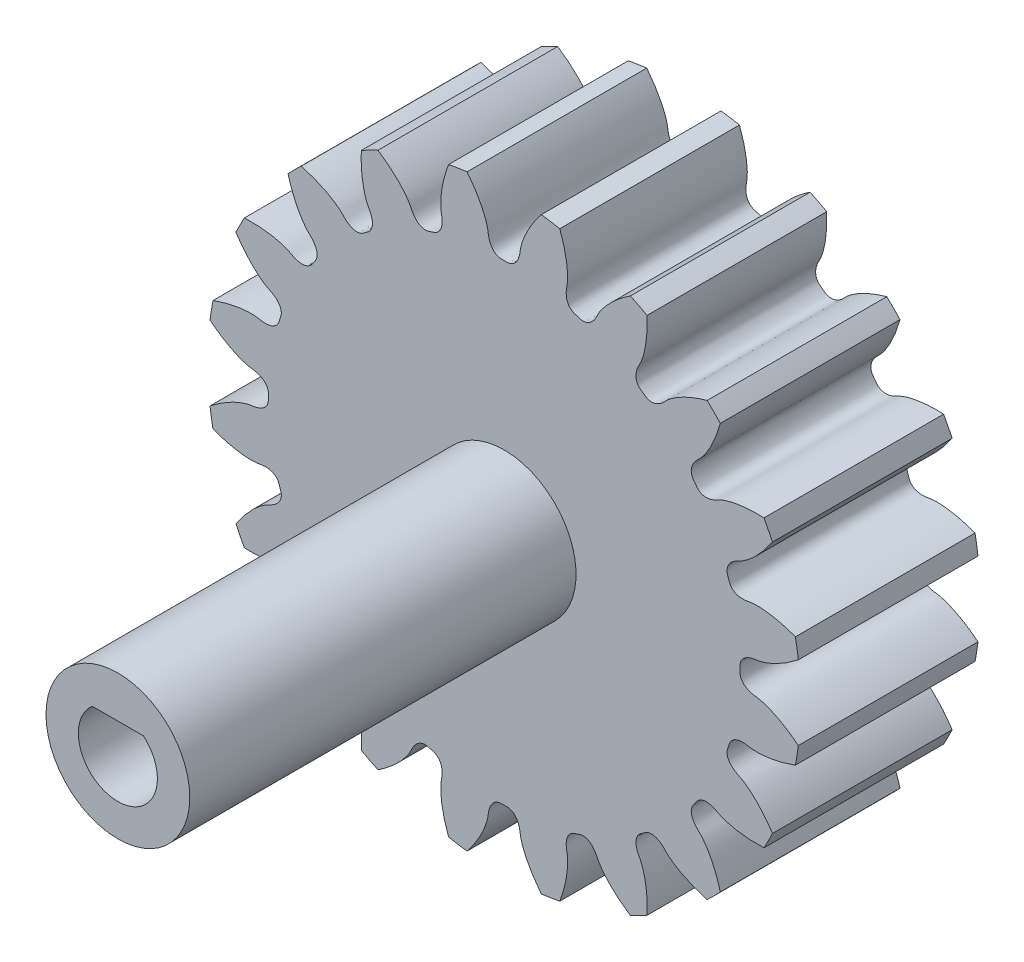
SolidWorks part; units mm, degrees
ref_plane "Front Plane" through (0, 0, 0) normal (0, 0, 1) x (1, 0, 0)
ref_plane "Top Plane" through (0, 0, 0) normal (0, 1, 0) x (1, 0, 0)
ref_plane "Right Plane" through (0, 0, 0) normal (1, 0, 0) x (0, 0, -1)
ref_axis "Axis1" through (0, 0, 55) along (0, 0, -1)
sketch "SketchRevolveSpurAssembly01Pinion" plane through (0, 0, 0) normal (1, 0, 0) x (0, 0, -1)
  line L0 (0, 0) -> (1, 0) construction
  line L1 (-5, 0) -> (-5, 16.5)
  line L2 (-5, 16.5) -> (5, 16.5)
  line L3 (5, 16.5) -> (5, 0)
  line L4 (5, 0) -> (-5, 0)
  dimension "Side1" = 5
  dimension "OutsideRadius" = 16.5
  dimension "Side2" = 5
revolve "SpurAssembly01Pinion" add sketch "SketchRevolveSpurAssembly01Pinion" angle 360 about L0
sketch "SketchToothSpurAssembly01Pinion" plane through (0, 0, 0) normal (0, 0, 1) x (1, 0, 0)
  arc A0 (16.4388, 2.1204) -> (16.4388, -2.1204) centre (0, 0) cw
  spline S0 degree 3 poles (16.4388, -2.1204) (16.3062, -2.0126) (16.1079, -1.8609) (15.8417, -1.6767) (15.6549, -1.5557) (15.4759, -1.4476) (15.3054, -1.3516) (15.1441, -1.2672) (14.9923, -1.1937) (14.8506, -1.1305) (14.7196, -1.0767) (14.5996, -1.0318) (14.491, -0.9949) (14.3942, -0.9653) (14.3096, -0.9423) (14.2375, -0.925) (14.178, -0.9126) (14.0492, -0.8903) (13.9123, -0.8782) (13.7697, -0.8427) (13.6956, -0.8206) (13.6244, -0.795) (13.5557, -0.7654) (13.4893, -0.7311) (13.4248, -0.6913) (13.3623, -0.6446) (13.3021, -0.5892) (13.2452, -0.523) (13.1943, -0.4439) (13.1533, -0.3509) (13.1303, -0.2534) (13.1208, -0.135) (13.1277, 0) (13.1208, 0.135) (13.1303, 0.2534) (13.1533, 0.3509) (13.1943, 0.4439) (13.2452, 0.523) (13.3021, 0.5892) (13.3623, 0.6446) (13.4248, 0.6913) (13.4893, 0.7311) (13.5557, 0.7654) (13.6244, 0.795) (13.6956, 0.8206) (13.7697, 0.8427) (13.9123, 0.8782) (14.0492, 0.8903) (14.178, 0.9126) (14.2375, 0.925) (14.3096, 0.9423) (14.3942, 0.9653) (14.491, 0.9949) (14.5996, 1.0318) (14.7196, 1.0767) (14.8506, 1.1305) (14.9923, 1.1937) (15.1441, 1.2672) (15.3054, 1.3516) (15.4759, 1.4476) (15.6549, 1.5557) (15.8417, 1.6767) (16.1079, 1.8609) (16.3062, 2.0126) (16.4388, 2.1204) knots 0 0 0 0 0.061423 0.08971 0.11638 0.141434 0.164872 0.186693 0.206898 0.225486 0.242459 0.257814 0.271554 0.283677 0.294183 0.303073 0.310347 0.316004 0.350077 0.359568 0.368803 0.377844 0.386769 0.395676 0.404689 0.413963 0.423683 0.434051 0.445256 0.457401 0.47042 0.481067 0.5 0.518933 0.52958 0.542599 0.554744 0.565949 0.576317 0.586037 0.595311 0.604324 0.613231 0.622156 0.631197 0.640432 0.649923 0.683996 0.689653 0.696927 0.705817 0.716323 0.728446 0.742186 0.757541 0.774514 0.793102 0.813307 0.835128 0.858566 0.88362 0.91029 0.938577 1 1 1 1
extrude "ToothExtrudeCutSpurAssembly01Pinion" cut sketch "SketchToothSpurAssembly01Pinion" against normal blind 5 and the other way blind 5
pattern_circular "PatternSpurAssembly01Pinion" count 20 over 360 about axis through (0, 0, 55) along (0, 0, -1) of "ToothExtrudeCutSpurAssembly01Pinion"
sketch "AuxiliarySketchSpurAssembly01Pinion" plane through (0, 0, 0) normal (0, 0, 1) x (1, 0, 0)
  circle A0 centre (0, 0) radius 15 construction
  circle A1 centre (0, 0) radius 14.0954 construction
  circle A2 centre (0, 0) radius 14.1048 construction
  circle A3 centre (0, 0) radius 16.5 construction
  circle A4 centre (0, 0) radius 13.125 construction
  dimension "PitchDiameter" = 30
  dimension "BaseDiameter" = 28.1908
  dimension "FormDiameter" = 28.2095
  dimension "MajorDiameter" = 33
  dimension "MinorDiameter" = 26.25
sketch "Sketch1" plane through (0, 0, 5) normal (0, 0, 1) x (1, 0, 0)
  circle A0 centre (0, 0) radius 4
extrude "Boss-Extrude1" add sketch "Sketch1" along normal blind 21.5
sketch "Sketch7" plane through (0, 0, 26.5) normal (0, 0, 1) x (1, 0, 0)
  line L0 (0, 0) -> (0, 1.6803) construction
  line L1 (1.4201, 1.6803) -> (-1.4201, 1.6803)
  circle A0 centre (0, 0) radius 2.2 construction
  arc A1 (1.4201, 1.6803) -> (-1.4201, 1.6803) centre (0, 0) cw
  point P10 (0, 1.6803)
extrude "Cut-Extrude5" cut sketch "Sketch7" against normal blind 8 contours L1 A1
sketch "Sketch8" plane through (0, 0, -5) normal (0, 0, -1) x (-1, 0, 0)
  circle A0 centre (0, 0) radius 4
extrude "Boss-Extrude5" add sketch "Sketch8" along normal blind 5
